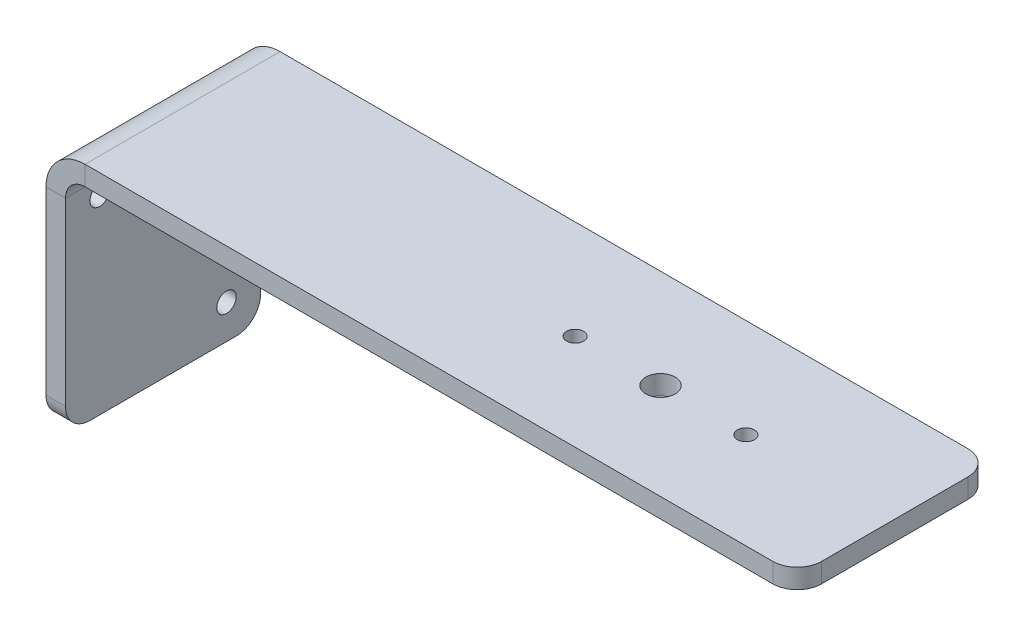
SolidWorks part; units mm, degrees
note: The reader was unsure of these and kept them because the rebuilt part matched: flange length of "Edge-Flange1".
ref_plane "Front Plane" through (0, 0, 0) normal (0, 0, 1) x (1, 0, 0)
ref_plane "Top Plane" through (0, 0, 0) normal (0, 1, 0) x (1, 0, 0)
ref_plane "Right Plane" through (0, 0, 0) normal (1, 0, 0) x (0, 0, -1)
sketch "Sketch1" plane through (0, 0, 0) normal (0, 1, 0) x (1, 0, 0)
  line L1 (0, 0) -> (150, 0)
  line L2 (0, 0) -> (0, 40)
  line L3 (0, 40) -> (150, 40)
  line L4 (150, 0) -> (150, 40)
  dimension "D1" = 40
  dimension "D2" = 150
base flange "Base-Flange1" sketch "Sketch1" thickness 4 reverse thickness direction no parameters "D1"=4
edge flange "Edge-Flange1" sketch "Sketch8" flange angle 90 flange length 50 flange position material outside bend radius 4 thickness 4 relief rectangular parameters "D6"=10
sketch "Sketch8" plane through (0, -4, 0) normal (-1, 0, 0) x (0, 0, -1)
  line L0 (40, 0) -> (0, 0) construction
  line L1 (40, 0) -> (0, 0)
  line L2 (0, 0) -> (0, 46)
  line L3 (0, 46) -> (40, 46)
  line L4 (40, 46) -> (40, 0)
bend "EdgeBend1" bend radius 4 bend angle 90 parameters "D5"=1
sketch "Sketch9" plane through (0, 0, 0) normal (1, 0, 0) x (0, 0, -1)
  line L0 (0, -50) -> (0, -8) construction
  line L1 (40, -8) -> (40, -50) construction
  line L2 (40, -50) -> (0, -50) construction
  line L3 (40, -4) -> (0, -4) construction
  circle A0 centre (7, -11) radius 2
  circle A1 centre (33, -43) radius 2
  dimension "D1" = 4
  dimension "D2" = 7
  dimension "D3" = 7
  dimension "D4" = 7
  dimension "D5" = 7
extrude "Cut-Extrude1" cut sketch "Sketch9" against normal blind 10 normal cut yes
fillet "Fillet1" radius 5 4 edges at (150, -2, -40) (150, -2, 0) (-2, -50, -40) (-2, -50, 0)
sketch "Sketch10" plane through (0, 0, 0) normal (0, 1, 0) x (1, 0, 0)
  circle A0 centre (102.2635, 19.7096) radius 3.0098
  circle A1 centre (119.7635, 19.7096) radius 1.75
  circle A2 centre (84.7635, 19.7096) radius 1.75
  point P6 (0, 0)
  point P7 (105.6335, 19.5224)
  point P8 (102.2635, 19.7096)
  dimension "D1" = 35
  dimension "D2" = 3.5
  dimension "D3" = 17.5
extrude "Cut-Extrude2" cut sketch "Sketch10" against normal blind 10 normal cut yes
sketch "Bend-Lines1" plane through (0, 0, 0) normal (0, 1, 0) x (1, 0, 0)
sketch "Bounding-Box1" plane through (0, 0, 0) normal (0, 1, 0) x (1, 0, 0)
sheet metal parameters "Sheet-Metal1" thickness 4 parameters "D1"=12
flat pattern "Flat-Pattern1" [suppressed]
sketch "Bend-Lines2" plane through (0, 0, 0) normal (0, 1, 0) x (1, 0, 0)
sketch "Bounding-Box2" [suppressed] plane through (0, 0, 0) normal (0, 1, 0) x (1, 0, 0)
sheet metal parameters "Sheet-Metal2" thickness 4 parameters "D1"=12
flat pattern "Flat-Pattern1" [suppressed]
sketch "Bend-Lines2" plane through (0, 0, 0) normal (0, 1, 0) x (1, 0, 0)
sketch "Bounding-Box2" [suppressed] plane through (0, 0, 0) normal (0, 1, 0) x (1, 0, 0)
bend of the flat pattern "Flatten-<EdgeBend1>1"
sheet metal parameters "Sheet-Metal3" thickness 4 parameters "D1"=12
flat pattern "Flat-Pattern1" [suppressed]
sketch "Bend-Lines2" plane through (0, 0, 0) normal (0, 1, 0) x (1, 0, 0)
sketch "Bounding-Box2" [suppressed] plane through (0, 0, 0) normal (0, 1, 0) x (1, 0, 0)
bend of the flat pattern "Flatten-<EdgeBend1>1"
sheet metal parameters "Sheet-Metal4" thickness 4 parameters "D1"=12
flat pattern "Flat-Pattern1" [suppressed]
sketch "Bend-Lines2" plane through (0, 0, 0) normal (0, 1, 0) x (1, 0, 0)
sketch "Bounding-Box2" [suppressed] plane through (0, 0, 0) normal (0, 1, 0) x (1, 0, 0)
bend of the flat pattern "Flatten-<EdgeBend1>1"
